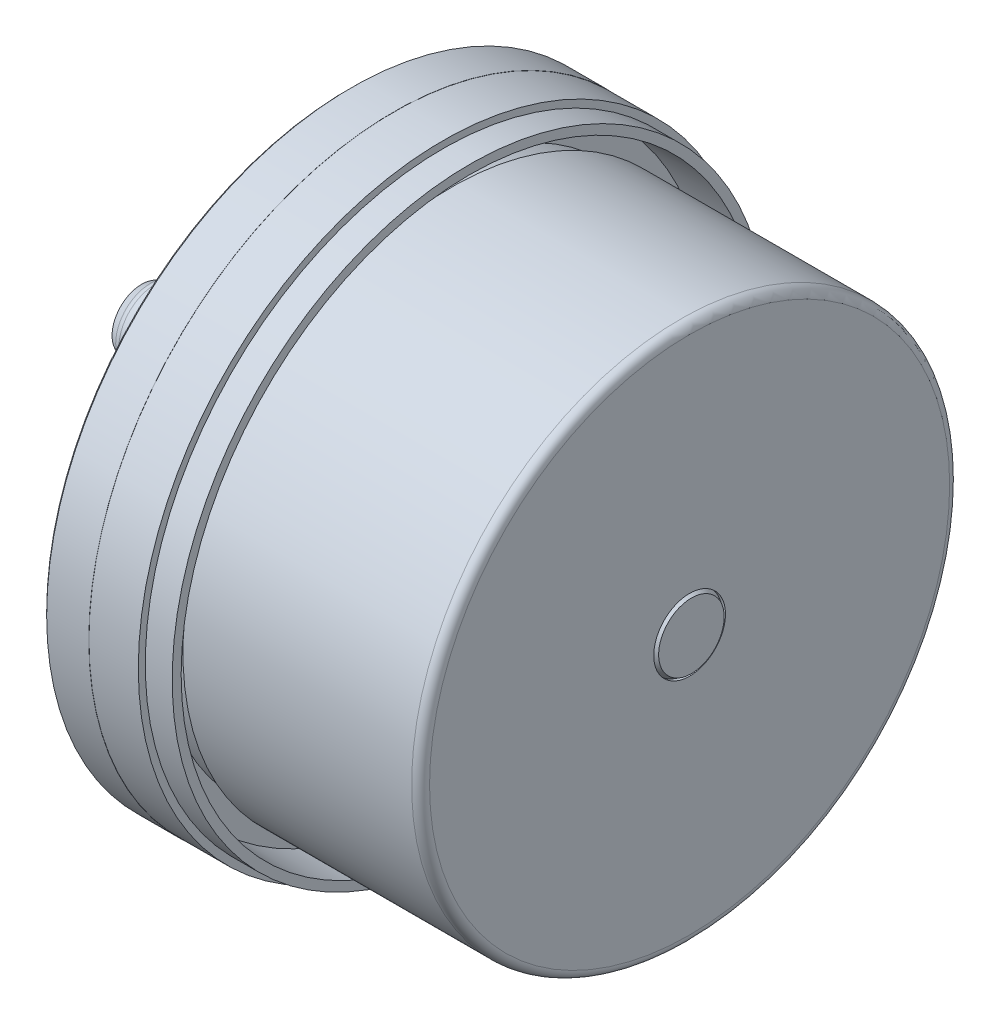
SolidWorks part; units mm, degrees
ref_plane "Front Plane" through (0, 0, 0) normal (0, 0, 1) x (1, 0, 0)
ref_plane "Top Plane" through (0, 0, 0) normal (0, 1, 0) x (1, 0, 0)
ref_plane "Right Plane" through (0, 0, 0) normal (1, 0, 0) x (0, 0, -1)
sketch "Sketch1" plane through (0, 0, 0) normal (0, 0, 1) x (1, 0, 0)
  line L0 (-23.1, 3.3072) -> (-23.1, 0)
  line L1 (-23.1, 0) -> (38.2, 0)
  line L2 (38.2, 0) -> (38.2, 3.6536)
  line L3 (38.2, 3.6536) -> (37.6, 4)
  line L4 (37.6, 4) -> (38, 4)
  line L5 (38, 4) -> (38, 30)
  line L6 (38, 30) -> (11.5, 30)
  line L7 (11.5, 30) -> (11.5, 29)
  line L8 (11.5, 29) -> (7.8, 29)
  line L9 (7.8, 29) -> (7.8, 32.001)
  line L10 (7.8, 32.001) -> (13.5, 32.2)
  line L11 (13.5, 32.2) -> (13.5, 33.2)
  line L12 (13.5, 33.2) -> (10.5, 33.2)
  line L13 (10.5, 33.2) -> (10.5, 33.98)
  line L14 (10.5, 33.98) -> (5, 33.98)
  line L15 (5, 33.98) -> (5, 34)
  line L16 (5, 34) -> (0, 34)
  line L17 (0, 34) -> (0, 11.2887)
  line L18 (0, 11.2887) -> (0.5, 11)
  line L19 (0.5, 11) -> (-2.6, 11)
  line L20 (-2.6, 11) -> (-2.6, 4.5)
  line L21 (-2.1, 4) -> (-21.9, 4)
  line L22 (-21.9, 4) -> (-23.1, 3.3072)
  line L23 (-23.1, 0) -> (38.2, 0) construction
  arc A0 (-2.6, 4.5) -> (-2.1, 4) centre (-2.1, 4.5) ccw
revolve "Revolve1" add sketch "Sketch1" angle 360 about L23 reverse direction yes
hole_wizard "Ø3.3 (3.3) Diameter Hole1" positions "Sketch3" profile "Sketch2" hole size "Ø3.3" standard "ANSI Metric"
sketch "Sketch3" plane through (0, 0, 0) normal (-1, 0, 0) x (0, 0, 1)
  point P0 (0, 21.5)
  point P1 (18.6195, -10.75)
  point P2 (-18.6195, -10.75)
sketch "Sketch2" plane through (0, 21.5, 0) normal (0, 1, 0) x (0, 0, 1)
  line L0 (0, 0) -> (0, 8.2914)
  line L1 (0, 8.2914) -> (1.65, 7.3)
  line L2 (1.65, 7.3) -> (1.65, 0)
  line L5 (1.65, 0) -> (0, 0)
  line L10 (0, 8.2914) -> (-1.65, 7.3) construction
  line L11 (0, -6.35) -> (0, 107.95) construction
  dimension "Hole Dia." = 3.3
  dimension "Hole Depth" = 7.3
  dimension "Drill Angle" = 118
chamfer "Chamfer1" distance 0.55 angle 45 3 edges at (0, 21.5, 1.65) (0, -10.75, 20.2695) (0, -10.75, -16.9695)
chamfer "Chamfer2" distance 0.3 angle 45 1 edges at (0, 0, -34)
fillet "Fillet1" radius 0.5 1 edges at (-2.6, 0, -11) tangent propagation no
fillet "Fillet2" radius 1 2 edges at (38, 0, -30) (-21.9, 0, -4) tangent propagation no
ref_axis "Axis1" through (-21.6321, 0, 0) along (1, 0, 0)
ref_plane "Plane1" through (0, 0, 0) normal (-1, 0, 0) x (0, 0, 1)
